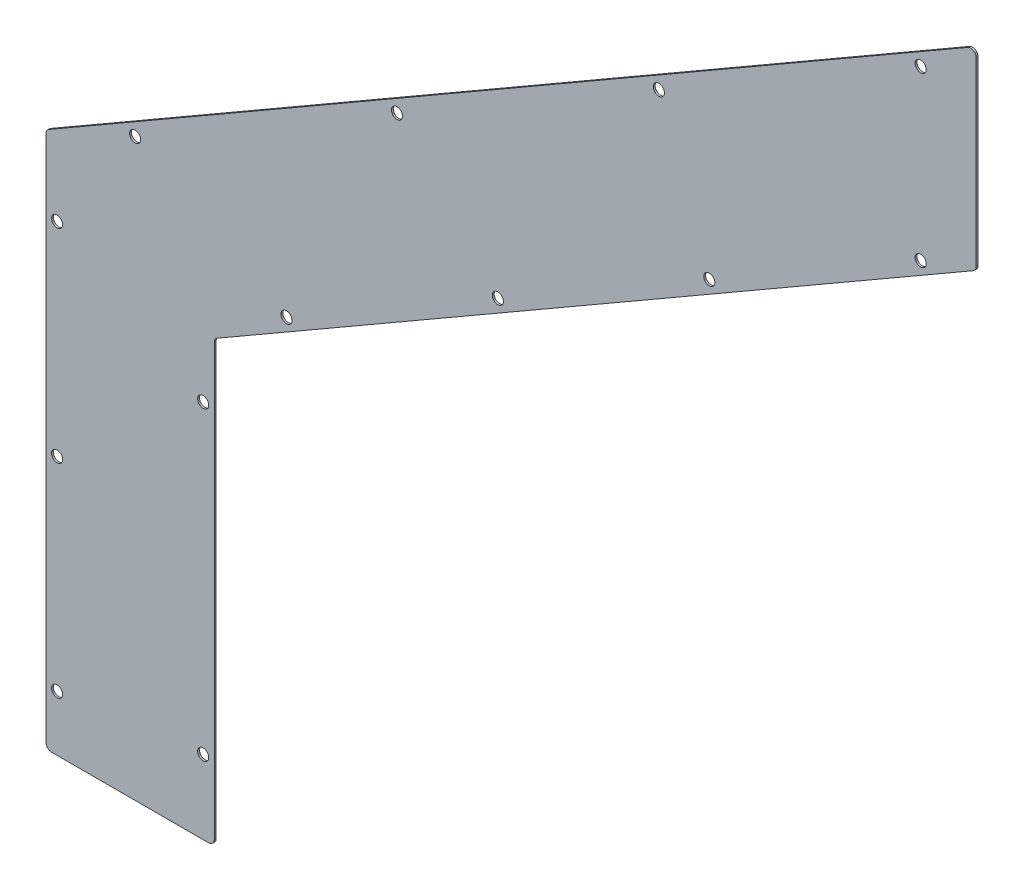
SolidWorks part; units mm, degrees
ref_plane "Front Plane" through (0, 0, 0) normal (0, 0, 1) x (1, 0, 0)
ref_plane "Top Plane" through (0, 0, 0) normal (0, 1, 0) x (1, 0, 0)
ref_plane "Right Plane" through (0, 0, 0) normal (1, 0, 0) x (0, 0, -1)
sketch "Sketch1" plane through (0, 0, 0) normal (0, 0, 1) x (1, 0, 0)
  line L0 (0, 0) -> (0, 237.7367)
  line L1 (0, 237.7367) -> (412, 475.605)
  line L2 (412, 475.605) -> (412, 580.4172)
  line L3 (412, 580.4172) -> (-91, 290.01)
  line L4 (-91, 290.01) -> (-91, 0)
  line L5 (-91, 0) -> (0, 0)
  dimension "D1" = 91
  dimension "D2" = 90.77
  dimension "D3" = 120
  dimension "D4" = 290.01
  dimension "D5" = 503
base flange "Base-Flange1" sketch "Sketch1" thickness 1 reverse thickness direction no parameters "D1"=1
fillet "Fillet1" radius 3 6 edges at (-91, 290.01, -0.5) (-91, 0, -0.5) (0, 0, -0.5) (0, 237.7367, -0.5) (412, 475.605, -0.5) (412, 580.4172, -0.5)
sketch "Sketch2" plane through (0, 0, -1) normal (0, 0, -1) x (-1, 0, 0)
  line L3 (-407.5, 577.8191) -> (89.5, 290.876) construction
  line L4 (-412, 477.3371) -> (-412, 575.221) construction
  line L5 (-1.5, 238.6027) -> (-410.5, 474.739) construction
  line L6 (91, 288.2779) -> (91, 3) construction
  line L7 (0, 3) -> (0, 236.0047) construction
  line L8 (88, 0) -> (3, 0) construction
  circle A0 centre (-382, 556.1685) radius 3
  circle A1 centre (-240.4048, 474.4185) radius 3
  circle A2 centre (-98.8097, 392.6685) radius 3
  circle A3 centre (42.7855, 310.9185) radius 3
  circle A4 centre (-382, 465.2127) radius 3
  circle A5 centre (-267.6846, 399.2127) radius 3
  circle A6 centre (-153.3693, 333.2127) radius 3
  circle A7 centre (-39.0539, 267.2127) radius 3
  circle A8 centre (85, 30) radius 3
  circle A9 centre (6, 40) radius 3
  circle A10 centre (85, 140) radius 3
  circle A11 centre (85, 250) radius 3
  circle A12 centre (6, 205) radius 3
  point P4 (-412, 575.221)
  point P5 (91, 288.2779)
  dimension "D1" = 6
  dimension "D2" = 6
  dimension "D3" = 30
  dimension "D4" = 4
  dimension "D5" = 6
  dimension "D7" = 6
  dimension "D8" = 6
  dimension "D9" = 30
  dimension "D12" = 40
  dimension "D6" = 4
  dimension "D10" = 3
  dimension "D11" = 2
extrude "Cut-Extrude1" cut sketch "Sketch2" against normal blind 10 normal cut yes
sketch "Bend-Lines1" [suppressed] plane through (0, 0, 0) normal (0, 1, 0) x (1, 0, 0)
sketch "Bounding-Box1" [suppressed] plane through (0, 0, 0) normal (0, 1, 0) x (1, 0, 0)
sheet metal parameters "Sheet-Metal1" thickness 1 parameters "D1"=1
flat pattern "Flat-Pattern1" [suppressed]
sketch "Bend-Lines2" plane through (0, 0, 0) normal (0, 1, 0) x (1, 0, 0)
sketch3d "Bounding-Box2" [suppressed]
  line L0 (-43.7412, -49.1571, 0) -> (450.6346, 527.7985, 0) construction
  line L1 (-246.7602, 124.8037, 0) -> (247.6157, 701.7593, 0) construction
  line L2 (-43.7412, -49.1571, 0) -> (-246.7602, 124.8037, 0) construction
  line L3 (450.6346, 527.7985, 0) -> (247.6157, 701.7593, 0) construction
sheet metal parameters "Sheet-Metal2" thickness 1 parameters "D1"=1
flat pattern "Flat-Pattern1"
sketch "Bend-Lines2" plane through (0, 0, 0) normal (0, 1, 0) x (1, 0, 0)
sketch3d "Bounding-Box2" [suppressed]
  line L0 (-39.2537, -43.3136, 0) -> (461.6923, 533.4269, 0) construction
  line L1 (-233.4669, 125.3764, 0) -> (267.4791, 702.1169, 0) construction
  line L2 (-39.2537, -43.3136, 0) -> (-233.4669, 125.3764, 0) construction
  line L3 (461.6923, 533.4269, 0) -> (267.4791, 702.1169, 0) construction
